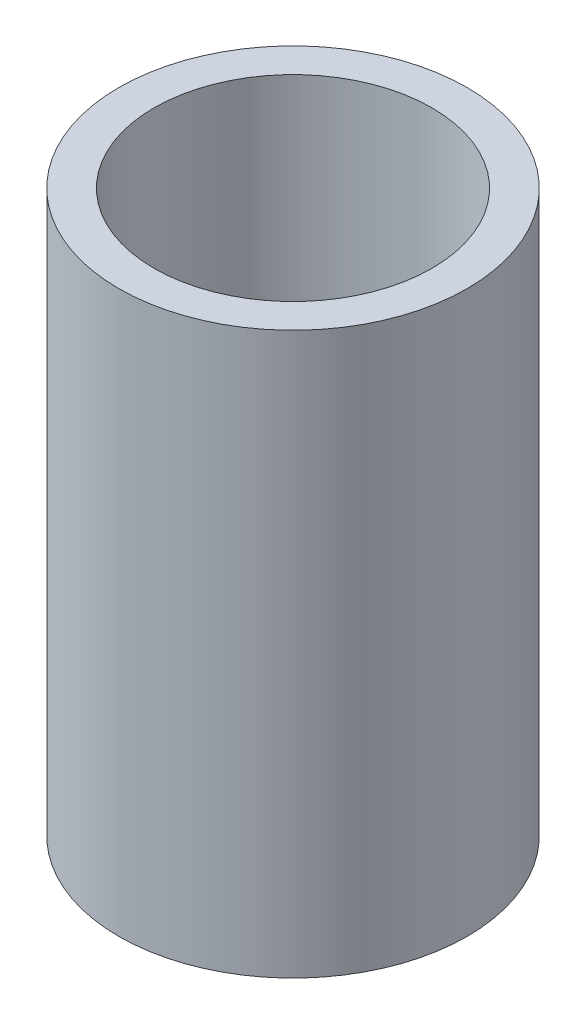
SolidWorks part; units mm, degrees
ref_plane "Front Plane" through (0, 0, 0) normal (0, 0, 1) x (1, 0, 0)
ref_plane "Top Plane" through (0, 0, 0) normal (0, 1, 0) x (1, 0, 0)
ref_plane "Right Plane" through (0, 0, 0) normal (1, 0, 0) x (0, 0, -1)
sketch "Sketch1" plane through (0, 0, 0) normal (0, 1, 0) x (1, 0, 0)
  circle A0 centre (0, 0) radius 15
  dimension "SLEEVE_OD" = 30
extrude "Boss-Extrude1" add sketch "Sketch1" along normal blind 48.3229
sketch "Sketch2" plane through (0, 0, 0) normal (0, 1, 0) x (1, 0, 0)
  circle A0 centre (0, 0) radius 11.9722
  dimension "BORE_D" = 23.9443
extrude "Cut-Extrude1" cut sketch "Sketch2" along normal through all
chamfer "Chamfer1" distance 1.9562 angle 30 rebuild error yes
